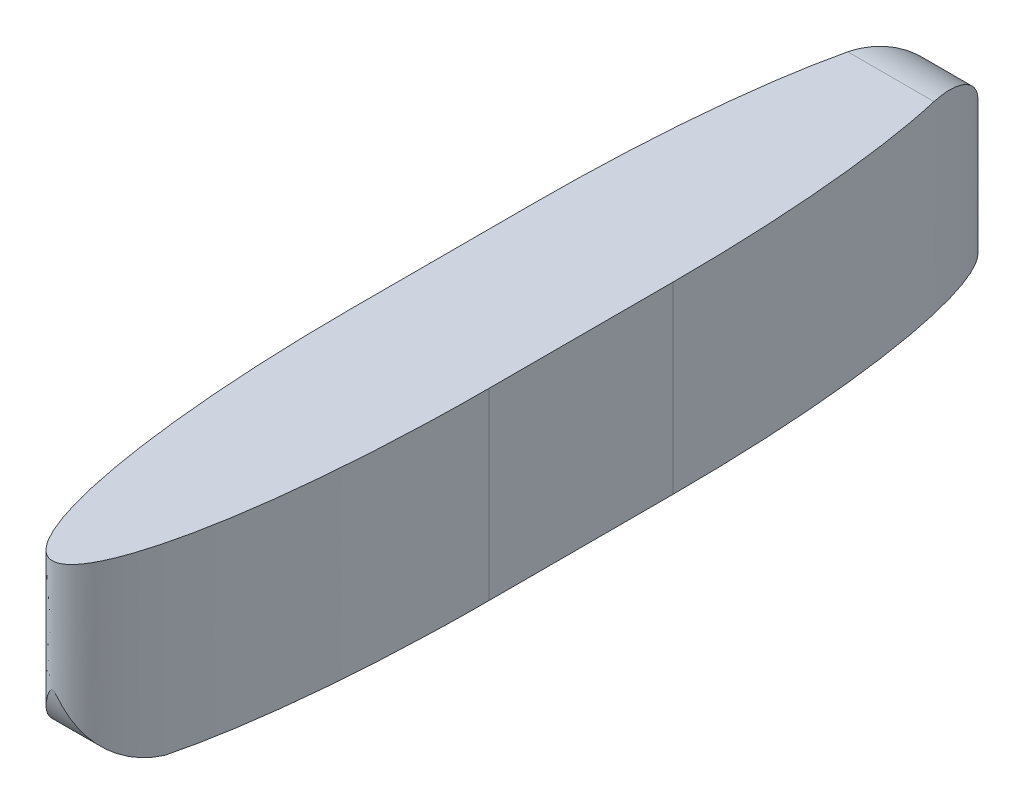
SolidWorks part; units mm, degrees
ref_plane "Front Plane" through (0, 0, 0) normal (0, 0, 1) x (1, 0, 0)
ref_plane "Top Plane" through (0, 0, 0) normal (0, 1, 0) x (1, 0, 0)
ref_plane "Right Plane" through (0, 0, 0) normal (1, 0, 0) x (0, 0, -1)
sketch "Sketch5" plane through (0, 0, 0) normal (0, 1, 0) x (1, 0, 0)
  line L1 (0, 0) -> (300, 0)
  line L2 (0, 0) -> (0, 400)
  line L3 (0, 400) -> (300, 400)
  line L4 (300, 0) -> (300, 400)
  dimension "D1" = 300
  dimension "D2" = 400
extrude "Boss-Extrude1" add sketch "Sketch5" along normal blind 400
sketch "Sketch11" plane through (0, 400, 0) normal (0, 1, 0) x (1, 0, 0)
  line L0 (300, 400) -> (0, 400) construction
  line L2 (0, 400) -> (300, 400)
  line L3 (300, 400) -> (0, 400)
  line L4 (300, 400) -> (0, 400)
  line L5 (300, 0) -> (0, 0)
  ellipse E0 centre (150, 0) end of major axis (150, -800) minor radius 150 (0, 0) -> (300, 0) ccw
  ellipse E2 centre (150, 400) end of major axis (150, -400) minor radius 150 (300, 400) -> (0, 400) ccw
  dimension "D1" = 800
  dimension "D2" = 800
extrude "Boss-Extrude3" add sketch "Sketch11" against normal blind 400 contours E0 E2 | L3 E0 region at (150, 400, -739.4622) region at (150, 400, 339.4622)
sketch "Sketch13" plane through (0, 0, 0) normal (1, 0, 0) x (0, 0, -1)
  line L0 (-800, 400) -> (-800, 0) construction
  line L1 (-800, 0) -> (0, 0) construction
  line L3 (-800, 200) -> (-800, 0)
  line L4 (-800, 0) -> (-643.3538, 0)
  line L5 (0, 400) -> (400, 0) construction
  line L6 (200, 400) -> (200, 0) construction
  line L7 (0, 400) -> (400, 400) construction
  line L8 (0, 0) -> (400, 0) construction
  line L9 (1200.2629, 199.9571) -> (1200, 400)
  line L10 (1200, 400) -> (400, 400) construction
  line L11 (1200, 400) -> (1043.6166, 399.9571)
  arc A0 (-800, 200) -> (-643.3538, 0) centre (-621.6769, 178.3231) ccw
  arc A1 (1200.2629, 199.9571) -> (1043.6166, 399.9571) centre (1021.9398, 221.634) ccw
extrude "Cut-Extrude1" cut sketch "Sketch13" along normal blind 400 contours A0 L3 L4 region at (0, 38.6995, 761.3005)
sketch "Sketch18" plane through (0, 0, 0) normal (1, 0, 0) x (0, 0, -1)
  line L0 (1200, 0) -> (1200, 400) construction
  line L1 (1200, 400) -> (400, 400) construction
  line L2 (1200, 218.287) -> (1200, 400)
  line L3 (1200, 400) -> (1024.4106, 400)
  arc A0 (1200, 218.287) -> (1024.4106, 400) centre (1021.3488, 221.3488) ccw
extrude "Cut-Extrude2" cut sketch "Sketch18" along normal blind 400 contours A0 L2 L3 region at (0, 360.1212, -1160.1212)
